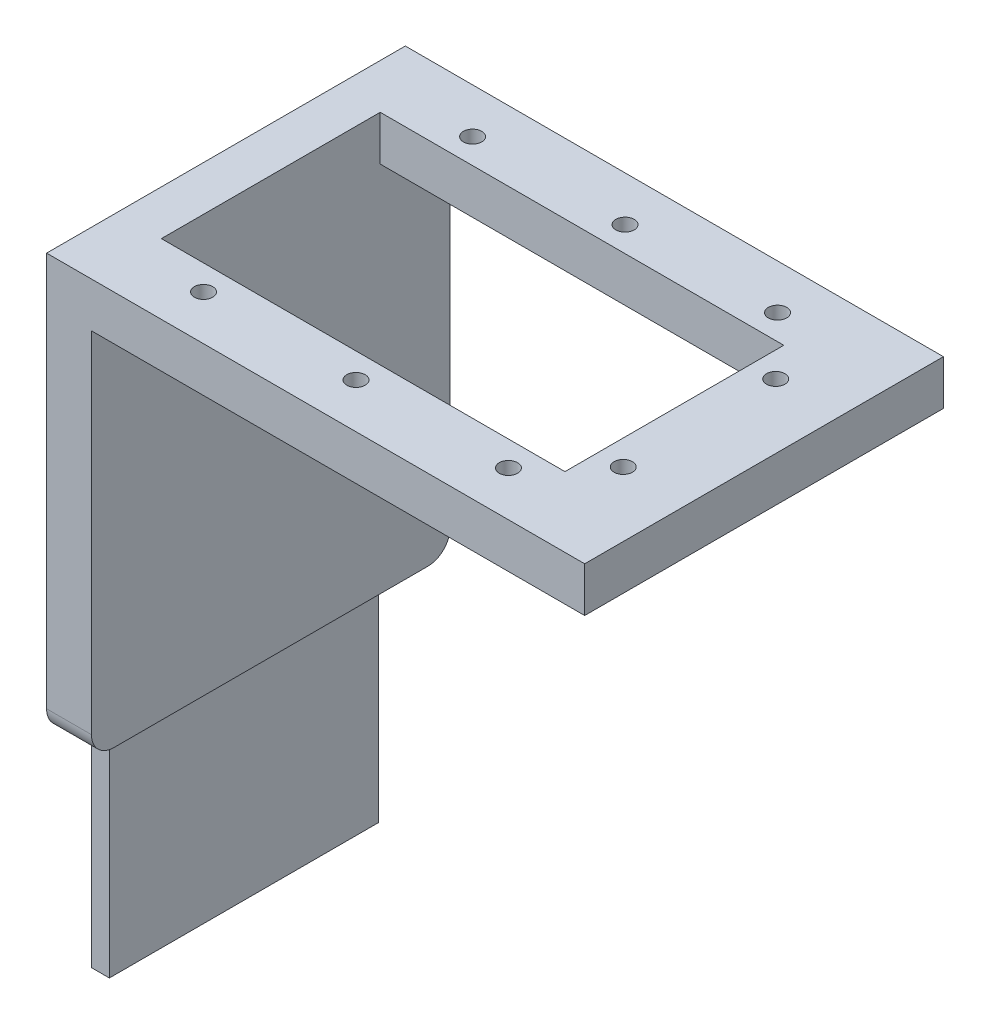
SolidWorks part; units mm, degrees
material "ABS"
ref_plane "Front Plane" through (0, 0, 0) normal (0, 0, 1) x (1, 0, 0)
ref_plane "Top Plane" through (0, 0, 0) normal (0, 1, 0) x (1, 0, 0)
ref_plane "Right Plane" through (0, 0, 0) normal (1, 0, 0) x (0, 0, -1)
sketch "Sketch1" plane through (0, 0, 0) normal (0, 1, 0) x (1, 0, 0)
  line L1 (0, 0) -> (60, 0)
  line L2 (0, 0) -> (0, 40)
  line L3 (0, 40) -> (60, 40)
  line L4 (60, 0) -> (60, 40)
  line L5 (5, 7.8) -> (50, 7.8)
  line L6 (5, 7.8) -> (5, 32.2)
  line L7 (5, 32.2) -> (50, 32.2)
  line L8 (50, 7.8) -> (50, 32.2)
  point P9 (5, 20)
  point P10 (0, 20)
  dimension "D1" = 40
  dimension "D2" = 60
  dimension "D3" = 45
  dimension "D4" = 24.4
  dimension "D5" = 5
extrude "Boss-Extrude1" add sketch "Sketch1" along normal blind 5
sketch "Sketch6" plane through (0, 0, 0) normal (0, -1, 0) x (1, 0, 0)
  line L0 (0, -40) -> (0, 0) construction
  line L1 (0, -40) -> (5, -40)
  line L2 (0, -40) -> (0, 0)
  line L3 (0, 0) -> (5, 0)
  line L4 (5, -40) -> (5, 0)
  line L5 (0, 0) -> (60, 0) construction
  line L6 (5, -32.2) -> (5, -7.8) construction
  line L7 (60, -40) -> (0, -40) construction
extrude "Boss-Extrude4" add sketch "Sketch6" along normal blind 41.5
sketch "Sketch7" plane through (0, -41.5, 0) normal (0, -1, 0) x (-1, 0, 0)
  line L0 (-5, 0) -> (0, 0) construction
  line L1 (-2, 35) -> (0, 35)
  line L2 (-2, 35) -> (-2, 5)
  line L3 (-2, 5) -> (0, 5)
  line L4 (0, 35) -> (0, 5)
  line L6 (-2.5, 40) -> (-2.5, 0) construction
  line L7 (0, 40) -> (-5, 40) construction
  line L8 (0, 0) -> (0, 40) construction
  point P10 (-2, 20)
  point P17 (0, 20)
  dimension "D1" = 2
  dimension "D2" = 30
extrude "Boss-Extrude5" add sketch "Sketch7" along normal blind 25
fillet "Fillet2" radius 2.5 1 edges at (2, -41.5, -20)
fillet "Fillet3" radius 2.5 4 edges at (2.25, -41.5, -5) (2.25, -41.5, -35) (2.5, -41.5, 0) (2.5, -41.5, -40)
sketch "Sketch8" plane through (0, 0, 0) normal (0, -1, 0) x (-1, 0, 0)
  line L0 (-1060, 20) -> (48940, 20) construction
  line L1 (-60, 0) -> (-60, 40) construction
  circle A0 centre (-46.5, 5) radius 1.025
  circle A1 centre (-29.5, 5) radius 1.025
  circle A2 centre (-12.5, 5) radius 1.025
  circle A3 centre (-52.8, 11.5) radius 1.025
  circle A4 centre (-12.5, 35) radius 1.025
  circle A5 centre (-29.5, 35) radius 1.025
  circle A6 centre (-46.5, 35) radius 1.025
  circle A7 centre (-52.8, 28.5) radius 1.025
  point P17 (-60, 20)
extrude "Cut-Extrude1" cut sketch "Sketch8" against normal up to next
